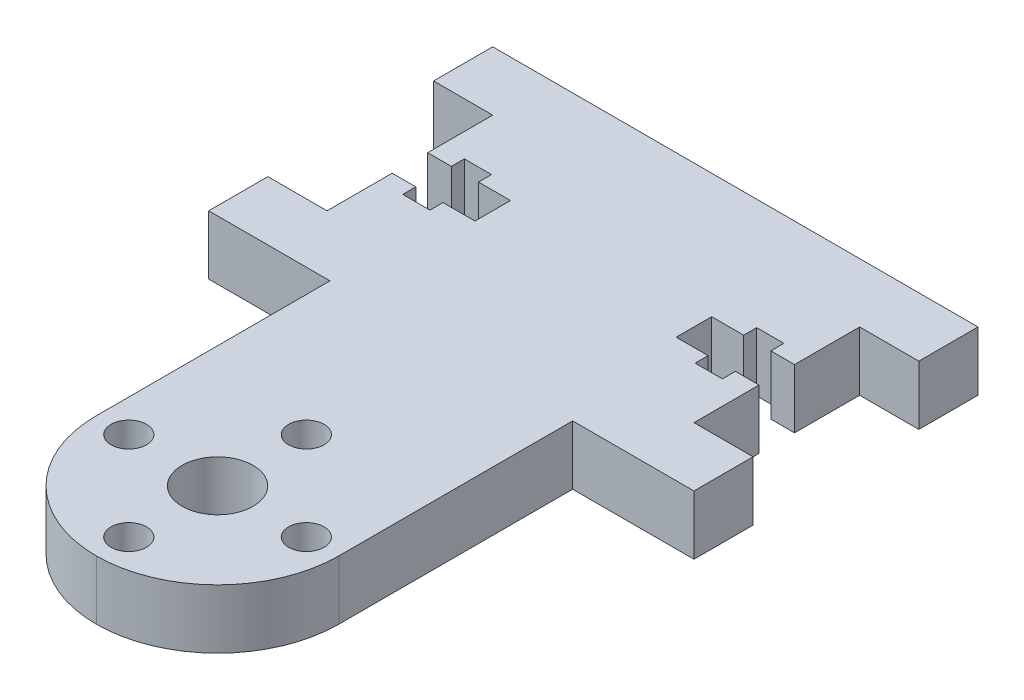
SolidWorks part; units mm, degrees
ref_plane "Front Plane" through (0, 0, 0) normal (0, 0, 1) x (1, 0, 0)
ref_plane "Top Plane" through (0, 0, 0) normal (0, 1, 0) x (1, 0, 0)
ref_plane "Right Plane" through (0, 0, 0) normal (1, 0, 0) x (0, 0, -1)
sketch "Sketch1" plane through (0, 0, 0) normal (0, 1, 0) x (1, 0, 0)
  line L0 (51.3755, 21.289) -> (44.3755, 18.289) construction
  line L1 (44.3755, 7.789) -> (75.3755, 7.789)
  line L2 (44.3755, 31.789) -> (75.3755, 31.789)
  line L3 (75.3755, 12.789) -> (75.3755, 18.289)
  line L4 (59.8755, 31.789) -> (59.8755, 7.789) construction
  line L5 (51.3755, 18.289) -> (44.3755, 21.289) construction
  line L6 (44.3755, 7.789) -> (39.3755, 7.789)
  line L7 (39.3755, 7.789) -> (39.3755, 12.789)
  line L8 (44.3755, 12.789) -> (44.3755, 18.289)
  line L9 (71.0755, 17.189) -> (73.3755, 17.189)
  line L10 (68.3755, 18.289) -> (71.0755, 18.289)
  line L11 (68.3755, 18.289) -> (68.3755, 21.289)
  line L12 (68.3755, 21.289) -> (71.0755, 21.289)
  line L13 (68.3755, 18.289) -> (75.3755, 21.289) construction
  line L14 (68.3755, 21.289) -> (75.3755, 18.289) construction
  line L15 (71.0755, 21.289) -> (71.0755, 22.389)
  line L16 (71.0755, 22.389) -> (73.3755, 22.389)
  line L17 (73.3755, 21.289) -> (73.3755, 22.389)
  line L18 (73.3755, 18.289) -> (73.3755, 17.189)
  line L19 (71.0755, 18.289) -> (71.0755, 17.189)
  line L20 (73.3755, 21.289) -> (75.3755, 21.289)
  line L21 (73.3755, 18.289) -> (75.3755, 18.289)
  line L22 (75.3755, 21.289) -> (75.3755, 26.789)
  line L23 (75.3755, 12.789) -> (80.3755, 12.789)
  line L24 (75.3755, 31.789) -> (80.3755, 31.789)
  line L25 (75.3755, 26.789) -> (80.3755, 26.789)
  line L26 (80.3755, 31.789) -> (80.3755, 26.789)
  line L27 (80.3755, 7.789) -> (80.3755, 12.789)
  line L28 (75.3755, 7.789) -> (80.3755, 7.789)
  line L29 (39.3755, 31.789) -> (39.3755, 26.789)
  line L30 (44.3755, 26.789) -> (39.3755, 26.789)
  line L31 (44.3755, 31.789) -> (39.3755, 31.789)
  line L32 (44.3755, 12.789) -> (39.3755, 12.789)
  line L33 (44.3755, 21.289) -> (44.3755, 26.789)
  line L34 (46.3755, 18.289) -> (44.3755, 18.289)
  line L35 (46.3755, 21.289) -> (44.3755, 21.289)
  line L36 (48.6755, 18.289) -> (48.6755, 17.189)
  line L37 (46.3755, 18.289) -> (46.3755, 17.189)
  line L38 (46.3755, 21.289) -> (46.3755, 22.389)
  line L39 (48.6755, 22.389) -> (46.3755, 22.389)
  line L40 (48.6755, 21.289) -> (48.6755, 22.389)
  line L41 (51.3755, 21.289) -> (48.6755, 21.289)
  line L42 (51.3755, 18.289) -> (51.3755, 21.289)
  line L43 (51.3755, 18.289) -> (48.6755, 18.289)
  line L44 (48.6755, 17.189) -> (46.3755, 17.189)
  line L45 (68.3755, 19.789) -> (59.8755, 19.789) construction
  point P23 (47.8755, 19.789)
  point P25 (71.8755, 19.789)
  point P44 (59.8755, 19.789)
  point P49 (0, 0)
  dimension "D2" = 31
  dimension "D3" = 3
  dimension "D4" = 5
  dimension "D5" = 5
  dimension "D6" = 2
  dimension "D7" = 2.3
  dimension "D8" = 2.7
  dimension "D9" = 1.1
  dimension "D10" = 5
  dimension "D11" = 24
extrude "Boss-Extrude1" add sketch "Sketch1" along normal blind 5
sketch "Sketch2" plane through (0, 5, 0) normal (0, 1, 0) x (1, 0, 0)
  line L0 (59.8755, 26.125) -> (59.8755, 6.125) construction
  line L1 (59.8755, 6.125) -> (59.8755, -7.211) construction
  line L2 (59.8755, -22.211) -> (59.8755, -11.961) construction
  line L3 (49.6255, -22.211) -> (70.1255, -22.211)
  line L4 (49.6255, -22.211) -> (49.6255, 7.789)
  line L5 (49.6255, 7.789) -> (70.1255, 7.789)
  line L6 (70.1255, -22.211) -> (70.1255, 7.789)
  line L7 (49.6255, -22.211) -> (70.1255, 7.789) construction
  line L8 (49.6255, 7.789) -> (70.1255, -22.211) construction
  line L9 (59.8755, -11.961) -> (58.7867, -13.0498) construction
  line L10 (59.8755, -11.961) -> (67.1337, -19.2192) construction
  line L11 (59.8755, 31.789) -> (59.8755, 7.789) construction
  line L12 (80.3755, 31.789) -> (39.3755, 31.789) construction
  line L13 (39.3755, 7.789) -> (80.3755, 7.789) construction
  circle A0 centre (59.8755, -11.961) radius 3
  circle A1 centre (59.8755, -19.461) radius 1.5
  circle A6 centre (52.3755, -11.961) radius 1.5
  circle A7 centre (67.3755, -11.961) radius 1.5
  circle A8 centre (59.8755, -4.461) radius 1.5
  dimension "D3" = 6
  dimension "D5" = 3
  dimension "D1" = 30
  dimension "D2" = 20.5
  dimension "D4" = 10.25
  dimension "D6" = 7.5
  dimension "D7" = 45
  dimension "D8" = 45
extrude "Boss-Extrude2" add sketch "Sketch2" against normal blind 5
fillet "Fillet1" radius 10.25 2 edges at (49.6255, 2.5, 22.211) (70.1255, 2.5, 22.211)
